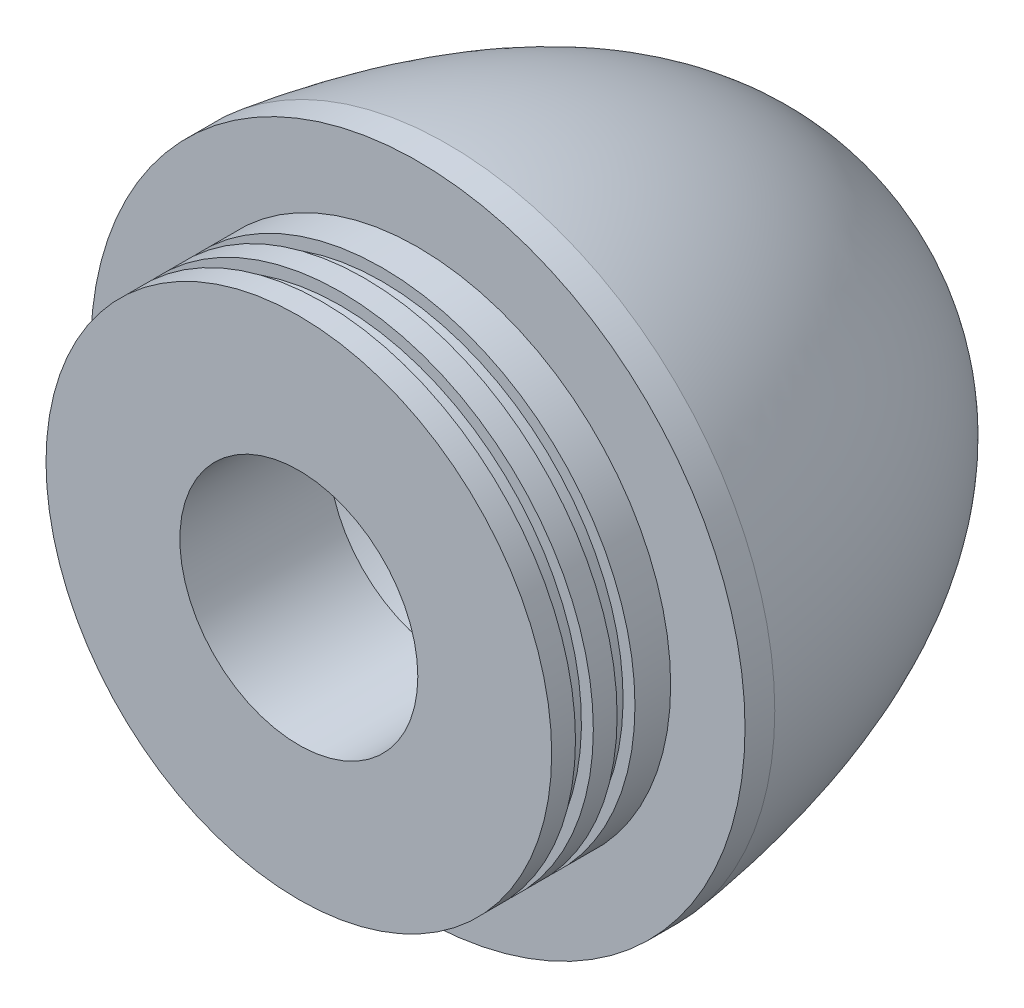
SolidWorks part; units mm, degrees
ref_plane "Front Plane" through (0, 0, 0) normal (0, 0, 1) x (1, 0, 0)
ref_plane "Top Plane" through (0, 0, 0) normal (0, 1, 0) x (1, 0, 0)
ref_plane "Right Plane" through (0, 0, 0) normal (1, 0, 0) x (0, 0, -1)
sketch "Sketch1" plane through (0, 0, 0) normal (0, 0, 1) x (1, 0, 0)
  circle A0 centre (0, 0) radius 55
  dimension "D1" = 110
extrude "Boss-Extrude1" add sketch "Sketch1" along normal blind 5
sketch "Sketch2" plane through (0, 0, 5) normal (0, 0, 1) x (1, 0, 0)
  circle A0 centre (0, 0) radius 42.5
  dimension "D1" = 85
extrude "Boss-Extrude2" add sketch "Sketch2" along normal blind 20
sketch "Sketch4" plane through (0, 0, 0) normal (1, 0, 0) x (0, 0, -1)
  line L0 (-5, 42.5) -> (-25, 42.5) construction
  line L5 (-14, 42.5) -> (-11, 42.5)
  line L6 (-14, 42.5) -> (-14, 40.5)
  line L7 (-14, 40.5) -> (-11, 40.5)
  line L8 (-11, 42.5) -> (-11, 40.5)
  line L9 (-21, 42.5) -> (-21, 40.5)
  line L10 (-5, 42.5) -> (-5, -42.5) construction
  line L11 (0, 0) -> (-33.7056, 0) construction
  line L12 (-21, 40.5) -> (-18, 40.5)
  line L13 (-18, 42.5) -> (-18, 40.5)
  line L14 (-21, 42.5) -> (-18, 42.5)
  point P8 (-11, 41.5)
  dimension "D1" = 3
  dimension "D2" = 6
  dimension "D3" = 2
  dimension "D4" = 4
revolve "Cut-Revolve1" cut sketch "Sketch4" angle 360 about L11
sketch "Sketch6" plane through (0, 0, 25) normal (0, 0, 1) x (1, 0, 0)
  circle A0 centre (0, 0) radius 20
  dimension "D1" = 40
extrude "Cut-Extrude1" cut sketch "Sketch6" against normal through all
sketch "Sketch5" plane through (0, 0, 0) normal (1, 0, 0) x (0, 0, -1)
  line L0 (0, 0) -> (70, 0) construction
  line L1 (0, -55) -> (0, 55) construction
  line L3 (-84.7685, -66.16) -> (84.7685, -43.84) construction
  line L4 (70, -118.5) -> (70, 118.5) construction
  line L5 (70, 0) -> (65, 0)
  line L7 (0, -55) -> (0, -49.9557)
  spline S0 degree 3 poles (70, 0) (70, -39.5) (28.2562, -51.28) (0, -55) knots 0 0 0 0 1 1 1 1
  spline S1 degree 1 poles (65, 0) (-0.6526, -50.0428) knots 0 0 1 1 construction
  spline S2 degree 3 poles (65, 0) (65, -0.5549) (64.9814, -1.6749) (64.8722, -3.8306) (64.6045, -6.4278) (64.0856, -9.3786) (63.1447, -13.1106) (61.5268, -17.4174) (58.9404, -22.0878) (55.7553, -26.3191) (50.7699, -31.4258) (43.2773, -36.8617) (32.8091, -41.9676) (23.3968, -45.1379) (15.7922, -47.1059) (10.1339, -48.3219) (5.5334, -49.1384) (2.23, -49.6452) (0.649, -49.868) (-0.2187, -49.9853) (-0.4877, -50.0211) (-0.6526, -50.0428) knots 0 0 0 0 0.015625 0.03125 0.0625 0.09375 0.125 0.1875 0.25 0.3125 0.375 0.5 0.625 0.75 0.8125 0.875 0.9375 0.96875 0.990159 0.994095 1 1 1 1
  dimension "D1" = 70
  dimension "D2" = 118.5
  dimension "D3" = 85.5
  dimension "D4" = 82.5
  dimension "D5" = 90
  dimension "D6" = 5
revolve "Revolve2" add sketch "Sketch5" angle 360 about L0 region at (0, -39.6343, -45.9938)
